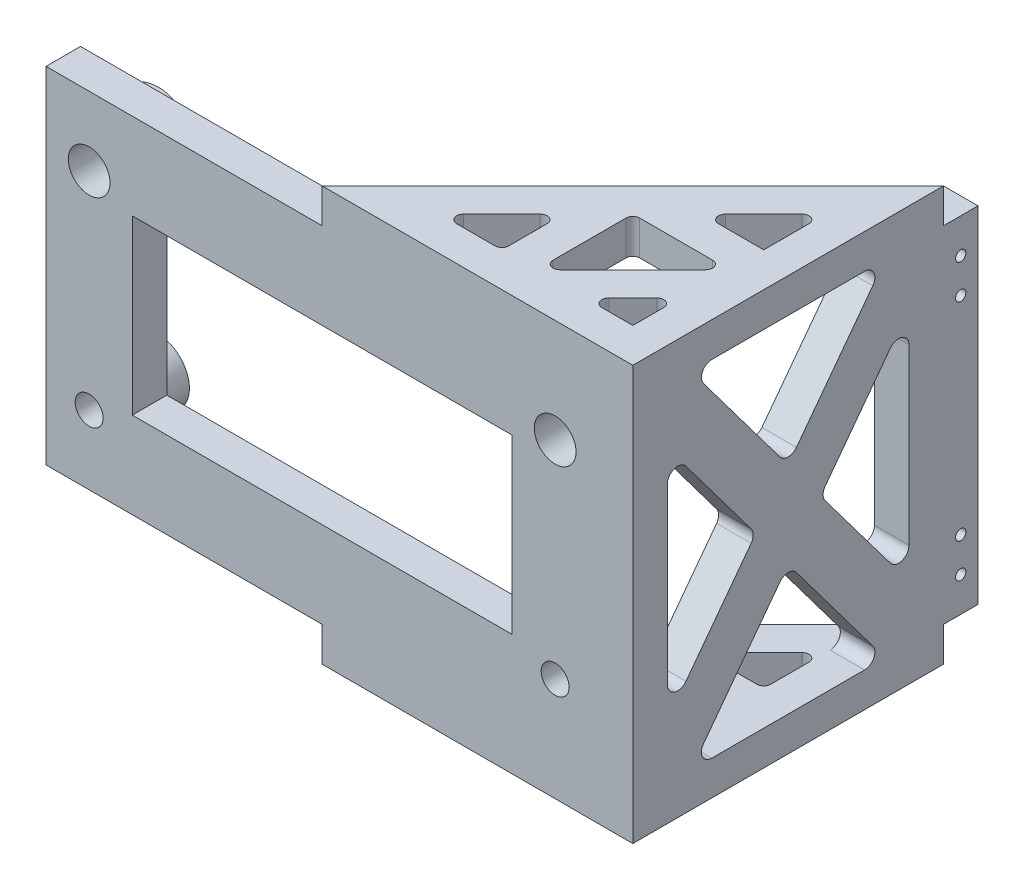
SolidWorks part; units mm, degrees
ref_plane "Front Plane" through (0, 0, 0) normal (0, 0, 1) x (1, 0, 0)
ref_plane "Top Plane" through (0, 0, 0) normal (0, 1, 0) x (1, 0, 0)
ref_plane "Right Plane" through (0, 0, 0) normal (1, 0, 0) x (0, 0, -1)
sketch "Sketch1" plane through (0, 0, 0) normal (0, 0, 1) x (1, 0, 0)
  line L5 (-55, -55) -> (55, -55)
  line L6 (-55, -55) -> (-55, -5)
  line L12 (-55, -5) -> (55, -5)
  line L13 (55, -55) -> (55, -5)
  line L20 (-80, -80) -> (80, -80)
  line L21 (-80, -80) -> (-80, 20)
  line L22 (-80, 20) -> (80, 20)
  line L23 (80, -80) -> (80, 20)
  line L26 (-67.5, -60) -> (67.5, -60) construction
  line L27 (-67.5, -60) -> (-67.5, 0) construction
  line L28 (-67.5, 0) -> (67.5, 0) construction
  line L29 (67.5, -60) -> (67.5, 0) construction
  circle A11 centre (-67.5, 0) radius 6.05
  circle A12 centre (67.5, 0) radius 6.05
  circle A14 centre (67.5, -60) radius 4.05
  circle A15 centre (-67.5, -60) radius 4.05
  point P0 (0, 0)
  point P6 (0, 0)
  point P11 (0, 0)
  dimension "D3" = 135
  dimension "D4" = 12.1
  dimension "D5" = 80
  dimension "D6" = 20
  dimension "D7" = 20
  dimension "D8" = 100
  dimension "D10" = 25
  dimension "D11" = 8.1
  dimension "D9" = 25
  dimension "D1" = 110
  dimension "D2" = 160
extrude "Boss-Extrude1" add sketch "Sketch1" along normal blind 10
sketch "Sketch4" plane through (0, 0, 10) normal (0, 0, 1) x (1, 0, 0)
  line L1 (80, 20) -> (90, 20)
  line L2 (80, 20) -> (80, -80)
  line L3 (80, -80) -> (90, -80)
  line L4 (90, 20) -> (90, -80)
  dimension "D1" = 10
extrude "Boss-Extrude3" add sketch "Sketch4" against normal blind 100
sketch "Sketch5" plane through (0, 0, 0) normal (0, 1, 0) x (1, 0, 0)
  line L0 (80, 70.7107) -> (9.2893, 0)
  line L1 (80, 90) -> (80, 0) construction
  line L2 (80, 0) -> (-80, 0) construction
  line L3 (80, 70.7107) -> (80, 0)
  line L4 (80, 0) -> (9.2893, 0)
  dimension "D1" = 100
  dimension "D2" = 45
ref_plane "Plane1" through (0, -30, 0) normal (0, 1, 0) x (1, 0, 0)
ref_plane "Plane3" through (0, -90, 0) normal (0, 1, 0) x (1, 0, 0)
ref_plane "Plane4" through (0, 25, 0) normal (0, 1, 0) x (1, 0, 0)
sketch "Sketch6" plane through (0, 25, 0) normal (0, 1, 0) x (1, 0, 0)
  line L0 (90, 90) -> (90, -10) construction
  line L1 (90, -10) -> (-80, -10) construction
  line L2 (90, 80) -> (90, -10)
  line L3 (90, -10) -> (0, -10)
  line L4 (0, -10) -> (90, 80)
  line L5 (24.1421, 0) -> (42.0711, 17.9289)
  line L9 (80, 0) -> (9.2893, 0) construction
  line L10 (80, 70.7107) -> (80, 0) construction
  line L11 (80, 55.8579) -> (80, 37.9289)
  line L12 (80, 27.9289) -> (52.0711, 0)
  line L13 (52.0711, 27.9289) -> (52.0711, 0)
  line L14 (52.0711, 27.9289) -> (80, 27.9289)
  line L15 (42.0711, 17.9289) -> (42.0711, 0)
  line L16 (62.0711, 37.9289) -> (80, 37.9289)
  line L17 (80, 13.7868) -> (66.2132, 0)
  line L18 (62.0711, 37.9289) -> (80, 55.8579)
  line L19 (80, 13.7868) -> (80, 0)
  line L20 (24.1421, 0) -> (42.0711, 0)
  line L21 (52.0711, 0) -> (66.2132, 0)
  line L22 (80, 0) -> (66.2132, 0)
  dimension "D1" = 45
  dimension "D2" = 90
  dimension "D3" = 10
  dimension "D4" = 10
  dimension "D5" = 10
  dimension "D6" = 10
sketch "Sketch8" plane through (0, -30, 0) normal (0, 1, 0) x (1, 0, 0)
  line L3 (80, 70.7107) -> (9.2893, 0)
  line L4 (9.2893, 0) -> (80, 0)
  line L5 (80, 0) -> (80, 70.7107)
  line L6 (80, 70.7107) -> (9.2893, 0)
  line L7 (9.2893, 0) -> (80, 0)
  line L8 (80, 0) -> (80, 70.7107)
  dimension "D1" = 0
extrude "Boss-Extrude4" add sketch "Sketch6" along normal mid plane 10 contours L4 L3 L2 L20 L5 L15 L16 L18 L11 L19 L22 L13 L14 L12 L17 region at (88.7272, 25, -35)
sketch "Sketch9" plane through (0, -90, 0) normal (0, 1, 0) x (1, 0, 0)
  line L0 (52.0711, 0) -> (66.2132, 0) construction
  line L1 (80, 27.9289) -> (52.0711, 0) construction
  line L2 (52.0711, 27.9289) -> (80, 27.9289) construction
  line L3 (52.0711, 27.9289) -> (52.0711, 0) construction
  line L4 (90, 80) -> (90, -10) construction
  line L5 (90, -10) -> (0, -10) construction
  line L6 (0, -10) -> (90, 80) construction
  line L7 (80, 13.7868) -> (66.2132, 0) construction
  line L8 (80, 13.7868) -> (80, 0) construction
  line L9 (80, 0) -> (66.2132, 0) construction
  line L10 (42.0711, 17.9289) -> (42.0711, 0) construction
  line L11 (24.1421, 0) -> (42.0711, 17.9289) construction
  line L12 (24.1421, 0) -> (42.0711, 0) construction
  line L13 (62.0711, 37.9289) -> (80, 37.9289) construction
  line L14 (62.0711, 37.9289) -> (80, 55.8579) construction
  line L15 (80, 55.8579) -> (80, 37.9289) construction
  line L16 (52.0711, 0) -> (66.2132, 0)
  line L17 (80, 27.9289) -> (52.0711, 0)
  line L18 (52.0711, 27.9289) -> (80, 27.9289)
  line L19 (52.0711, 27.9289) -> (52.0711, 0)
  line L20 (90, 80) -> (90, -10)
  line L21 (90, -10) -> (0, -10)
  line L22 (0, -10) -> (90, 80)
  line L23 (80, 13.7868) -> (66.2132, 0)
  line L24 (80, 13.7868) -> (80, 0)
  line L25 (80, 0) -> (66.2132, 0)
  line L26 (42.0711, 17.9289) -> (42.0711, 0)
  line L27 (24.1421, 0) -> (42.0711, 17.9289)
  line L28 (24.1421, 0) -> (42.0711, 0)
  line L29 (62.0711, 37.9289) -> (80, 37.9289)
  line L30 (62.0711, 37.9289) -> (80, 55.8579)
  line L31 (80, 55.8579) -> (80, 37.9289)
extrude "Boss-Extrude5" add sketch "Sketch9" along normal blind 10 contours L22 L21 L20 L28 L27 L26 L24 L25 L19 L18 L17 L23 L30 L31 L29 region at (88.7272, -90, -35)
sketch "Sketch12" plane through (90, 0, 0) normal (1, 0, 0) x (0, 0, -1)
  line L0 (25.625, -30) -> (0, -64.1667)
  line L1 (-10, -90) -> (-10, 30) construction
  line L3 (-10, 30) -> (80, -90) construction
  line L4 (55, -90) -> (-55, -90) construction
  line L5 (80, -80) -> (80, -90) construction
  line L6 (-10, -90) -> (80, 30) construction
  line L7 (0, -64.1667) -> (0, 4.1667)
  line L8 (0, 4.1667) -> (25.625, -30)
  line L9 (-56.0811, -30) -> (109.9016, -30) construction
  line L10 (35, 39.4519) -> (35, -98.5732) construction
  line L11 (35, -17.5) -> (6.875, 20)
  line L12 (6.875, 20) -> (63.125, 20)
  line L14 (80, 30) -> (-10, 30) construction
  line L15 (35, -17.5) -> (63.125, 20)
  line L16 (35, -42.5) -> (6.875, -80)
  line L17 (6.875, -80) -> (63.125, -80)
  line L18 (35, -42.5) -> (63.125, -80)
  line L19 (70, -64.1667) -> (70, 4.1667)
  line L20 (44.375, -30) -> (70, -64.1667)
  line L21 (70, 4.1667) -> (44.375, -30)
  point P3 (5, -30)
  point P19 (0, -30)
  point P31 (35, 20)
  dimension "D1" = 7.5
  dimension "D2" = 7.5
  dimension "D3" = 7.5
  dimension "D4" = 7.5
  dimension "D5" = 10
extrude "Cut-Extrude1" cut sketch "Sketch12" against normal blind 10
fillet "Fillet1" radius 3 12 edges at (85, -17.5, -35) (85, -42.5, -35) (85, 4.1667, 0) (85, -64.1667, 0) (85, -80, -6.875) (85, -64.1667, -70) (85, -80, -63.125) (85, 20, -63.125) (85, 4.1667, -70) (85, 20, -6.875) (85, -30, -44.375) (85, -30, -25.625)
fillet "Fillet2" radius 2 21 edges at (66.2132, 25, 0) (62.0711, 25, -37.9289) (24.1421, 25, 0) (80, 25, -13.7868) (80, 25, -55.8579) (42.0711, 25, -17.9289) (42.0711, 25, 0) (52.0711, 25, 0) (80, 25, -27.9289) (52.0711, 25, -27.9289) (66.2132, -85, 0) (52.0711, -85, 0) (42.0711, -85, 0) (62.0711, -85, -37.9289) (24.1421, -85, 0) (52.0711, -85, -27.9289) (80, -85, -27.9289) (42.0711, -85, -17.9289) (80, -85, -13.7868) (80, -85, -37.9289) (80, -85, -55.8579)
sketch "Sketch13" plane through (90, 0, 0) normal (1, 0, 0) x (0, 0, -1)
  line L0 (85, 20) -> (85, -80) construction
  line L1 (90, 20) -> (80, 20) construction
  line L2 (90, -80) -> (80, -80) construction
  circle A0 centre (85, 10) radius 1.5
  circle A1 centre (85, 0) radius 1.5
  circle A2 centre (85, -60) radius 1.5
  circle A3 centre (85, -70) radius 1.5
  dimension "D1" = 3
  dimension "D2" = 10
  dimension "D3" = 20
  dimension "D4" = 10
  dimension "D5" = 20
extrude "Cut-Extrude2" cut sketch "Sketch13" against normal blind 10
sketch "Sketch14" plane through (0, 0, 0) normal (0, 0, -1) x (-1, 0, 0)
  circle A0 centre (-67.5, 0) radius 11.05
  circle A1 centre (67.5, 0) radius 11.05
  circle A2 centre (67.5, -60) radius 9.05
  circle A3 centre (-67.5, -60) radius 9.05
  circle A4 centre (-67.5, 0) radius 6.05 construction
  circle A5 centre (67.5, 0) radius 6.05 construction
  circle A6 centre (-67.5, -60) radius 4.05 construction
  circle A7 centre (67.5, -60) radius 4.05 construction
  circle A8 centre (-67.5, -60) radius 4.05
  circle A9 centre (67.5, -60) radius 4.05
  circle A10 centre (67.5, 0) radius 6.05
  circle A11 centre (-67.5, 0) radius 6.05
  dimension "D1" = 5
  dimension "D2" = 5
extrude "Boss-Extrude10" add sketch "Sketch14" along normal blind 10
